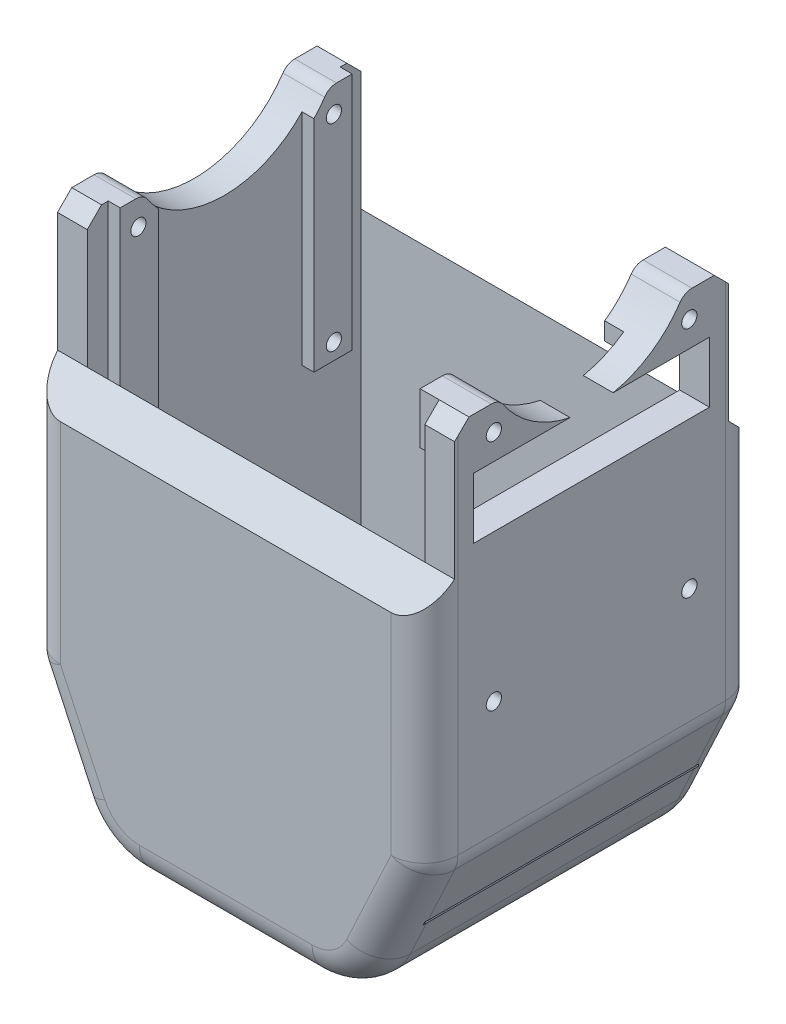
SolidWorks part; units mm, degrees
material "PLA"
ref_plane "Front Plane" through (0, 0, 0) normal (0, 0, 1) x (1, 0, 0)
ref_plane "Top Plane" through (0, 0, 0) normal (0, 1, 0) x (1, 0, 0)
ref_plane "Right Plane" through (0, 0, 0) normal (1, 0, 0) x (0, 0, -1)
sketch "Sketch1" plane through (0, 0, 0) normal (0, 0, 1) x (1, 0, 0)
  line L0 (0, 0) -> (35.4, 0)
  line L1 (35.4, 0) -> (35.4, 51.875)
  line L2 (0, 0) -> (-3.125, 0) construction
  line L3 (35.4, 0) -> (38.525, 0) construction
  line L4 (-3.125, -3.125) -> (38.525, -3.125)
  line L5 (38.525, -3.125) -> (38.525, 51.875)
  line L6 (-3.125, -3.125) -> (-3.125, 51.875)
  line L7 (0, 0) -> (0, 51.875)
  line L8 (0, 51.875) -> (-3.125, 51.875)
  line L9 (35.4, 51.875) -> (38.525, 51.875)
  dimension "D1" = 35.4
  dimension "D2" = 3.125
  dimension "D3" = 3.125
  dimension "D4" = 3.125
  dimension "D5" = 55
  dimension "D6" = 55
extrude "Boss-Extrude1" add sketch "Sketch1" along normal blind 28.72
sketch "Sketch2" plane through (38.525, 0, 0) normal (1, 0, 0) x (0, 0, -1)
  line L0 (-28.72, 46.285) -> (0, 46.285) construction
  line L1 (-28.72, -3.125) -> (-28.72, 51.875) construction
  line L2 (0, -3.125) -> (0, 51.875) construction
  line L3 (-28.72, 51.875) -> (0, 51.875) construction
  line L4 (-14.36, 46.285) -> (-14.36, 57.485) construction
  circle A0 centre (-14.36, 57.485) radius 11.2
  dimension "D1" = 5.59
  dimension "D2" = 11.2
extrude "Cut-Extrude1" cut sketch "Sketch2" against normal through all
fillet "Fillet2" radius 1.5 4 edges at (-1.5625, 51.875, 24.0537) (-1.5625, 51.875, 4.6663) (36.9625, 51.875, 4.6663) (36.9625, 51.875, 24.0537)
sketch "Sketch3" plane through (0, 0, 0) normal (0, 0, -1) x (-1, 0, 0)
  line L0 (-38.525, -3.125) -> (-38.525, 51.875) construction
  line L1 (-38.525, 37.875) -> (3.125, 37.875)
  line L2 (-38.525, 37.875) -> (-38.525, -3.125)
  line L3 (-38.525, -3.125) -> (3.125, -3.125)
  line L4 (3.125, 37.875) -> (3.125, -3.125)
  dimension "D1" = 0
extrude "Boss-Extrude2" add sketch "Sketch3" along normal blind 3.175
sketch "Sketch4" plane through (0, 0, 28.72) normal (0, 0, 1) x (1, 0, 0)
  line L1 (-3.125, 37.875) -> (38.525, 37.875)
  line L2 (-3.125, 37.875) -> (-3.125, -3.125)
  line L3 (-3.125, -3.125) -> (38.525, -3.125)
  line L4 (38.525, 37.875) -> (38.525, -3.125)
extrude "Boss-Extrude3" add sketch "Sketch4" along normal blind 3.175
chamfer "Chamfer1" distance 3.175 angle 45 2 edges at (17.7, 37.875, -3.175) (17.7, 37.875, 31.895)
chamfer "Chamfer2" distance 1.5 angle 45 4 edges at (-1.5625, 51.875, 0) (36.9625, 51.875, 0) (-1.5625, 51.875, 28.72) (36.9625, 51.875, 28.72)
chamfer "Chamfer4" distance 15 angle 25 1 edges at (38.525, -3.125, 14.36) first distance on face at (38.525, 38.9257, 14.36)
chamfer "Chamfer5" distance 5 angle 45 2 edges at (0, 0, 14.36) (35.4, 0, 14.36)
chamfer "Chamfer6" distance 15 angle 25 1 edges at (-3.125, -3.125, 14.36) first distance on face at (-3.125, 38.9257, 14.36)
sketch "Sketch5" plane through (0, 0, 0) normal (1, 0, 0) x (0, 0, -1)
  line L0 (-3.8368, 51.875) -> (-1.5, 51.875) construction
  line L2 (-2.2006, 51.875) -> (-2.2006, 26.7908)
  line L3 (-2.2006, 26.7908) -> (-6.2006, 26.7908)
  line L4 (-6.2006, 49.8127) -> (-6.2006, 26.7908)
  line L6 (-26.5194, 51.875) -> (-26.5194, 26.7908)
  line L7 (-26.5194, 26.7908) -> (-22.5194, 26.7908)
  line L8 (-22.5194, 49.8127) -> (-22.5194, 26.7908)
  line L9 (-27.22, 51.875) -> (-24.8832, 51.875) construction
  line L10 (-3.8368, 51.875) -> (-2.2006, 51.875)
  line L11 (-26.5194, 51.875) -> (-24.8832, 51.875)
  circle A0 centre (-24.61, 49.185) radius 0.8
  circle A1 centre (-24.61, 28.485) radius 0.8
  circle A2 centre (-4.11, 28.485) radius 0.8
  circle A3 centre (-4.11, 49.185) radius 0.8
  arc A4 (-3.8368, 51.875) -> (-5.0797, 51.2148) centre (-3.8368, 50.375) ccw construction
  arc A5 (-23.6403, 51.2148) -> (-5.0797, 51.2148) centre (-14.36, 57.485) ccw construction
  arc A6 (-23.6403, 51.2148) -> (-24.8832, 51.875) centre (-24.8832, 50.375) ccw construction
  arc A7 (-3.8368, 51.875) -> (-5.0797, 51.2148) centre (-3.8368, 50.375) ccw
  arc A8 (-23.6403, 51.2148) -> (-22.5194, 49.8127) centre (-14.36, 57.485) ccw
  arc A9 (-23.6403, 51.2148) -> (-24.8832, 51.875) centre (-24.8832, 50.375) ccw
  arc A10 (-6.2006, 49.8127) -> (-5.0797, 51.2148) centre (-14.36, 57.485) ccw
extrude "Boss-Extrude4" add sketch "Sketch5" along normal blind 1.25
sketch "Sketch6" plane through (0, 0, 0) normal (1, 0, 0) x (0, 0, -1)
  circle A0 centre (-24.61, 49.185) radius 0.8
  circle A1 centre (-24.61, 28.485) radius 0.8
  circle A2 centre (-4.11, 28.485) radius 0.8
  circle A3 centre (-4.11, 49.185) radius 0.8
extrude "Cut-Extrude2" cut sketch "Sketch6" against normal up to next
sketch "Sketch8" plane through (35.4, 0, 0) normal (-1, 0, 0) x (0, 0, 1)
  line L0 (7.86, 48.6376) -> (7.86, 45.835) construction
  line L1 (1.5, 51.875) -> (5.025, 51.875)
  line L2 (1.5, 51.875) -> (1.5, 46.5164)
  line L3 (1.5, 46.5164) -> (7.86, 46.5164)
  line L4 (7.86, 48.6376) -> (7.86, 46.5164)
  line L5 (20.86, 45.835) -> (20.86, 48.6376) construction
  line L6 (20.86, 46.5164) -> (27.22, 46.5164)
  line L7 (20.86, 46.5164) -> (20.86, 48.6376)
  line L8 (23.695, 51.875) -> (27.22, 51.875)
  line L9 (27.22, 46.5164) -> (27.22, 51.875)
  line L10 (28.72, 5) -> (28.72, 37.875) construction
  line L11 (28.72, 26.985) -> (0, 26.985)
  line L12 (28.72, 26.985) -> (28.72, 22.485)
  line L13 (28.72, 22.485) -> (0, 22.485)
  line L14 (0, 26.985) -> (0, 22.485)
  circle A0 centre (24.61, 49.185) radius 0.8
  circle A1 centre (4.11, 49.185) radius 0.8
  circle A2 centre (4.11, 24.735) radius 0.8
  circle A3 centre (24.61, 24.735) radius 0.8
  arc A4 (5.0077, 51.9039) -> (7.7768, 48.8089) centre (14.36, 57.485) ccw construction
  arc A5 (5.025, 51.875) -> (7.7768, 48.8089) centre (14.36, 57.485) ccw
  arc A6 (20.9432, 48.8089) -> (23.7123, 51.9039) centre (14.36, 57.485) ccw construction
  arc A7 (20.9432, 48.8089) -> (23.695, 51.875) centre (14.36, 57.485) ccw
  spline S0 degree 3 poles (-14965.5073, 909.3697) (-270.8827, -2.5945) (6.4526, 54.9166) (9.1755, 42.8182) (-228.7701, 57.3354) (6482.5839, -13476.4735) knots -187.819334 -187.819334 -187.819334 -187.819334 0.333333 0.666667 177.897266 177.897266 177.897266 177.897266 weights 1 1 1 1 1 1 only from (7.8374, 48.735) to (7.86, 48.6376) construction
  spline S1 degree 3 poles (-3212.9406, 14694.5622) (-126.742, -180.419) (3.9098, 53.479) (11.4663, 44.3699) (-173.2266, -102.9046) (3994.643, -14406.1016) knots -186.771693 -186.771693 -186.771693 -186.771693 0.333333 0.666667 175.978174 175.978174 175.978174 175.978174 weights 1 1 1 1 1 1 only from (7.7768, 48.8088) to (7.8374, 48.735) construction
  spline S2 degree 3 poles (7.8374, 48.735) (7.8425, 48.7246) (7.851, 48.7033) (7.8584, 48.6702) (7.86, 48.6485) (7.86, 48.6376) knots 0 0 0 0 0.333333 0.666667 1 1 1 1 weights 1 1 1 1 1 1
  spline S3 degree 3 poles (7.7768, 48.8088) (7.785, 48.8026) (7.8005, 48.7889) (7.8213, 48.7638) (7.8325, 48.745) (7.8374, 48.735) knots 0 0 0 0 0.333333 0.666667 1 1 1 1 weights 1 1 1 1 1 1
  spline S4 degree 3 poles (2030.5344, 14909.3671) (193.1002, -18.3637) (18.5786, 44.0268) (23.0621, 53.1925) (169.4146, -39.8412) (-8582.3581, -12234.9188) knots -78.350142 -78.350142 -78.350142 -78.350142 0.341381 0.67758 75.168746 75.168746 75.168746 75.168746 weights 1 1 1 1 1 1 only from (20.86, 48.6376) to (20.9432, 48.8089) construction
  spline S5 degree 3 poles (20.86, 48.6376) (20.86, 48.6599) (20.8668, 48.7046) (20.896, 48.7643) (20.9264, 48.7961) (20.9432, 48.8089) knots 0 0 0 0 0.341381 0.67758 1 1 1 1 weights 1 1 1 1 1 1
  point P42 (0, 24.735)
  line M9 (0, 37.875) -> (0, 5)
  line M11 (28.72, 5) -> (28.72, 37.875)
  line M14 (27.22, 51.875) -> (24.8832, 51.875)
  arc M15 (24.8832, 51.875) -> (23.6403, 51.2148) centre (24.8832, 50.375) ccw
  arc M16 (23.6403, 51.2148) -> (5.0797, 51.2148) centre (14.36, 57.485) cw
  arc M17 (5.0797, 51.2148) -> (3.8368, 51.875) centre (3.8368, 50.375) ccw
  line M18 (3.8368, 51.875) -> (1.5, 51.875)
  dimension "D1" = 4.5
extrude "Boss-Extrude5" add sketch "Sketch8" along normal blind 2 contours L6 L9 L7 A0 M14 M15 M16 | L4 L2 L3 A1 M16 M17 M18 | L13 L11 A3 A2 M11 M9 region at (35.4, 49.6068, 22.4374) region at (35.4, 51.7918, 2.6684) region at (35.4, 24.735, 14.36)
sketch "Sketch9" plane through (35.4, 0, 0) normal (-1, 0, 0) x (0, 0, 1)
  line L0 (24.61, 49.985) -> (24.61, 48.385) construction
  line L1 (4.11, 49.985) -> (4.11, 48.385) construction
  line L2 (4.11, 25.535) -> (4.11, 23.935) construction
  line L3 (24.61, 25.535) -> (24.61, 23.935) construction
  line L4 (26.72, 24.3748) -> (26.72, 51.0235) construction
  line L5 (26.72, 46.5147) -> (2, 46.5147)
  line L6 (26.72, 46.5147) -> (26.72, 40.1489)
  line L7 (26.72, 40.1489) -> (2, 40.1489)
  line L8 (2, 46.5147) -> (2, 40.1489)
  line L9 (2, 51.0235) -> (2, 24.3748) construction
  circle A0 centre (24.61, 24.735) radius 0.8
  circle A1 centre (4.11, 24.735) radius 0.8
  circle A2 centre (4.11, 49.185) radius 0.8
  circle A3 centre (24.61, 49.185) radius 0.8
extrude "Cut-Extrude4" cut sketch "Sketch9" against normal up to next
fillet "Fillet3" radius 7.5 2 edges at (3.8696, -3.125, 14.36) (31.5304, -3.125, 14.36)
fillet "Fillet4" radius 3.5 10 edges at (-0.6373, 6.5402, 31.895) (4.6179, -1.9504, 31.895) (36.0373, 6.5402, 31.895) (30.7821, -1.9504, 31.895) (36.0373, 6.5402, -3.175) (-0.6373, 6.5402, -3.175) (4.6179, -1.9504, -3.175) (17.7, -3.125, -3.175) (17.7, -3.125, 31.895) (30.7821, -1.9504, -3.175)
fillet "Fillet5" radius 3.5 5 edges at (38.525, 27.4284, 31.895) (38.525, 14.3007, 30.8699) (38.525, 27.4284, -3.175) (38.525, 14.3007, -2.1499) (38.525, 11.875, 14.36)
fillet "Fillet6" radius 3.5 5 edges at (-3.125, 27.4284, -3.175) (-3.125, 14.3007, -2.1499) (-3.125, 27.4284, 31.895) (-3.125, 14.3007, 30.8699) (-3.125, 11.875, 14.36)
